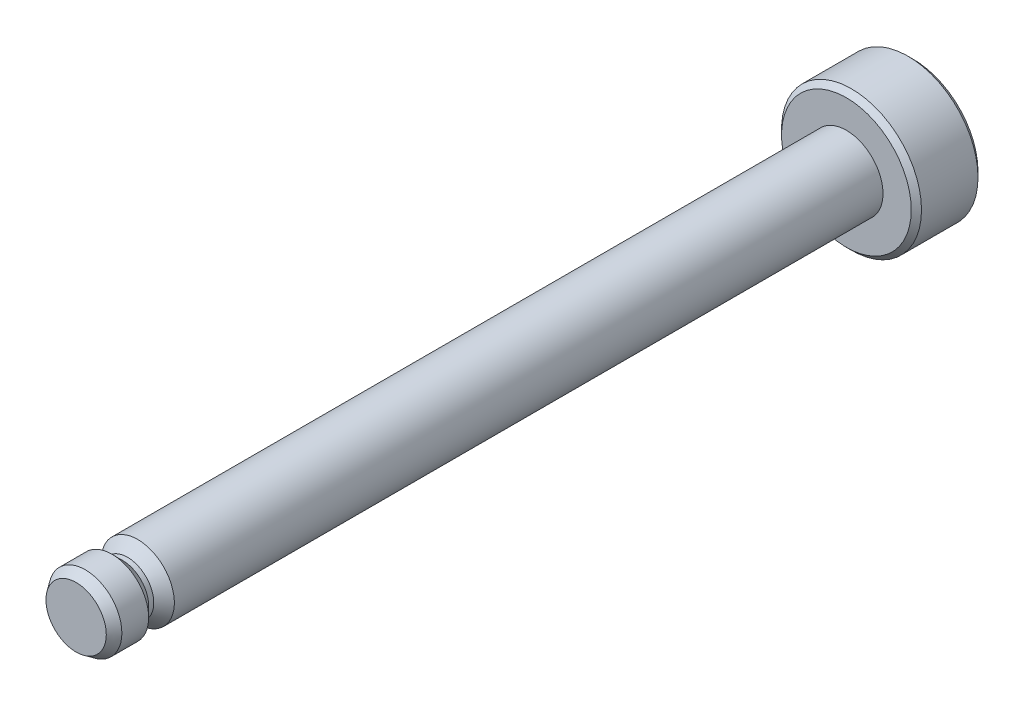
SolidWorks part; units mm, degrees
ref_plane "Front" through (0, 0, 0) normal (0, 0, 1) x (1, 0, 0)
ref_plane "Top" through (0, 0, 0) normal (0, 1, 0) x (1, 0, 0)
ref_plane "Right" through (0, 0, 0) normal (1, 0, 0) x (0, 0, -1)
sketch "Sketch2" plane through (0, 0, 0) normal (0, 0, 1) x (1, 0, 0)
  circle A0 centre (0, 0) radius 1.425
  dimension "D1" = 2.85
extrude "Shaft" add sketch "Sketch2" along normal blind 30
sketch "Sketch5" plane through (0, 0, 0) normal (0, 0, 1) x (1, 0, 0)
  circle A0 centre (0, 0) radius 2.725
  dimension "D1" = 5.45
extrude "Head" add sketch "Sketch5" against normal blind 2.6
sketch "Sketch4" plane through (0, 0, 0) normal (1, 0, 0) x (0, 0, -1)
  line L0 (0, 0) -> (-19.1, 0) construction
  line L1 (-19.1, 0) -> (-19.1, 4.3666) construction
  line L2 (-19.6, 1.425) -> (-18.6, 1.425)
  line L3 (0, 1.425) -> (-30, 1.425) construction
  line L6 (-18.6, 1.425) -> (-19, 1.025)
  line L7 (-19, 1.025) -> (-19.2, 1.025)
  line L8 (-19.2, 1.025) -> (-19.6, 1.425)
  line L9 (-19.1, 50) -> (-19.1, -50) construction
  dimension "D2" = 1
  dimension "D3" = 45
  dimension "D4" = 0.4
revolve "e-Clip Notch Short" [suppressed] cut sketch "Sketch4" angle 360 about L0
chamfer "Chamfer1" distance 0.25 angle 55 1 edges at (1.425, 0, 30) first distance on face at (1.425, 0, 30)
chamfer "Deburs" distance 0.2 angle 45 2 edges at (2.725, 0, 0) (2.725, 0, -2.6)
sketch "Sketch6" plane through (0, 0, 0) normal (1, 0, 0) x (0, 0, -1)
  line L0 (0, 0) -> (-28.1, 0) construction
  line L1 (-28.1, 0) -> (-28.1, 1.025) construction
  line L2 (0, 1.425) -> (-29.643, 1.425) construction
  line L3 (-28.6, 1.425) -> (-27.6, 1.425)
  line L4 (-27.6, 1.425) -> (-28, 1.025)
  line L5 (-28, 1.025) -> (-28.2, 1.025)
  line L6 (-28.2, 1.025) -> (-28.6, 1.425)
  line L7 (-28.1, 1.025) -> (-28.1, 1.425) construction
  line L8 (-19.6, 1.425) -> (-18.6, 1.425) construction
  line L9 (-19.2, 1.025) -> (-19.6, 1.425) construction
  point P16 (-26.1039, 1.0211)
  point P17 (0, 0)
revolve "e-Clip Notch Long" cut sketch "Sketch6" angle 360 about L0
equation "\"D1@Sketch2\"=\"Hardware Clearance Hole Diameter@Box Assy.Assembly\"-.3"
equation "\"D1@Sketch5\"=\"Hardware Head Countersink Diameter@Box Assy.Assembly\"-.3mm"
equation "\"D1@Head\"=\"Nut Trap Depth@Box Assy.Assembly\""
